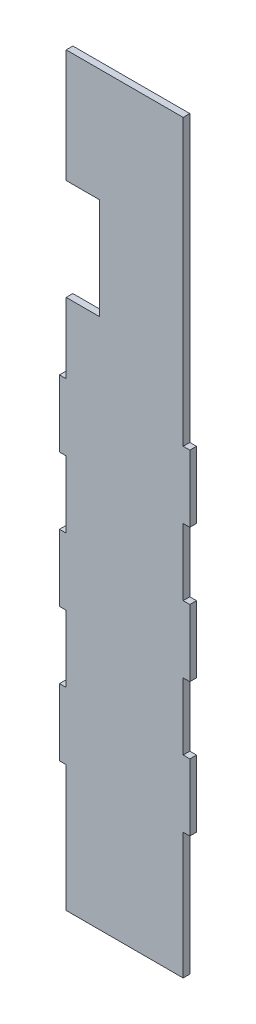
SolidWorks part; units mm, degrees
ref_plane "前视基准面" through (0, 0, 0) normal (0, 0, 1) x (1, 0, 0)
ref_plane "上视基准面" through (0, 0, 0) normal (0, 1, 0) x (1, 0, 0)
ref_plane "右视基准面" through (0, 0, 0) normal (1, 0, 0) x (0, 0, -1)
sketch "草图1" plane through (0, 0, 0) normal (0, 0, 1) x (1, 0, 0)
  line L38 (-8, 15.141) -> (-8, 49)
  line L39 (-8, 49) -> (27, 49)
  line L41 (-8, -15.141) -> (-8, -36.2215)
  line L42 (-8, -36.2215) -> (-10, -36.2215)
  line L43 (-10, -36.2215) -> (-10, -56.2215)
  line L44 (-10, -56.2215) -> (-8, -56.2215)
  line L45 (-8, -56.2215) -> (-8, -76.2215)
  line L46 (-8, -76.2215) -> (-10, -76.2215)
  line L47 (-10, -76.2215) -> (-10, -96.2215)
  line L48 (-10, -96.2215) -> (-8, -96.2215)
  line L49 (-8, -96.2215) -> (-8, -116.2215)
  line L52 (-8, -116.2215) -> (-10, -116.2215)
  line L53 (-10, -116.2215) -> (-10, -136.2215)
  line L54 (-10, -136.2215) -> (-8, -136.2215)
  line L55 (-8, -136.2215) -> (-8, -174)
  line L56 (-8, -174) -> (27, -174)
  line L58 (-8, -15.141) -> (2, -15.141)
  line L59 (2, -15.141) -> (2, 15.141)
  line L60 (2, 15.141) -> (-8, 15.141)
  line L61 (27, -136.2215) -> (27, -174)
  line L62 (29, -36.2215) -> (29, -56.2215)
  line L63 (29, -56.2215) -> (27, -56.2215)
  line L64 (27, -56.2215) -> (27, -76.2215)
  line L65 (27, -76.2215) -> (29, -76.2215)
  line L66 (29, -76.2215) -> (29, -96.2215)
  line L67 (29, -96.2215) -> (27, -96.2215)
  line L68 (27, -96.2215) -> (27, -116.2215)
  line L69 (29, -116.2215) -> (29, -136.2215)
  line L70 (29, -136.2215) -> (27, -136.2215)
  line L71 (27, -116.2215) -> (29, -116.2215)
  line L72 (27, 49) -> (27, -36.2215)
  line L73 (27, -36.2215) -> (29, -36.2215)
extrude "凸台-拉伸2" add sketch "草图1" along normal blind 2
